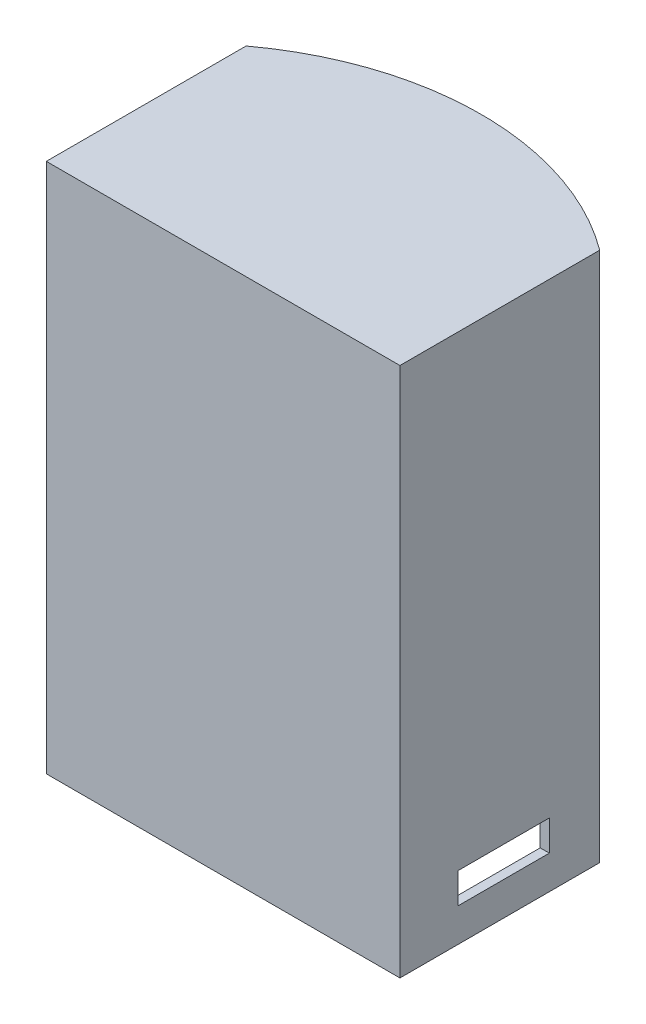
SolidWorks part; units mm, degrees
ref_plane "Front Plane" through (0, 0, 0) normal (0, 0, 1) x (1, 0, 0)
ref_plane "Top Plane" through (0, 0, 0) normal (0, 1, 0) x (1, 0, 0)
ref_plane "Right Plane" through (0, 0, 0) normal (1, 0, 0) x (0, 0, -1)
sketch "Sketch1" plane through (0, 0, 0) normal (0, 1, 0) x (1, 0, 0)
  line L0 (-29, -15) -> (-29, 15.7626)
  line L1 (-27.5, -15) -> (-16, -15)
  line L2 (-27.5, -15) -> (-27.5, 15)
  line L3 (29, -15) -> (29, 15.7626)
  line L4 (27.5, -15) -> (27.5, 15)
  line L5 (-27.5, -15) -> (27.5, 15) construction
  line L6 (-27.5, 15) -> (27.5, -15) construction
  line L8 (16, -15) -> (27.5, -15)
  line L9 (-27.5, -17) -> (-16, -17)
  line L10 (-16, -15) -> (-16, -17)
  line L12 (27.5, -17) -> (29, -17)
  line L13 (27.5, -17) -> (16, -17)
  line L14 (16, -15) -> (16, -17)
  line L15 (-29, -15) -> (-29, -17)
  line L16 (-29, -17) -> (-27.5, -17)
  line L17 (29, -17) -> (29, -15)
  arc A0 (-27.5, 15) -> (27.5, 15) centre (0, -23.3475) cw
  arc A1 (-29, 15.7626) -> (29, 15.7626) centre (0, -23.3475) cw
  point P0 (0, 0)
  dimension "D1" = 55
  dimension "D2" = 30
  dimension "D3" = 2
  dimension "D4" = 2
  dimension "D5" = 32
  dimension "D6" = 1.5
extrude "Boss-Extrude1" add sketch "Sketch1" along normal blind 85
sketch "Sketch3" plane through (0, 85, 0) normal (0, 1, 0) x (1, 0, 0)
  line L0 (-16, -17) -> (16, -17)
  line L10 (27.5, 15) -> (27.5, -15)
  line L11 (27.5, -15) -> (16, -15)
  line L12 (16, -15) -> (16, -17)
  line L13 (16, -17) -> (29, -17)
  line L14 (29, -17) -> (29, 15.7626)
  line L15 (-29, 15.7626) -> (-29, -17)
  line L16 (-29, -17) -> (-16, -17)
  line L17 (-16, -17) -> (-16, -15)
  line L18 (-16, -15) -> (-27.5, -15)
  line L19 (-27.5, -15) -> (-27.5, 15)
  line L23 (16, -17) -> (29, -17)
  line L24 (29, -17) -> (29, 15.7626)
  line L25 (-29, 15.7626) -> (-29, -17)
  line L26 (-29, -17) -> (-16, -17)
  arc A2 (27.5, 15) -> (-27.5, 15) centre (0, -23.3475) ccw
  arc A3 (29, 15.7626) -> (-29, 15.7626) centre (0, -23.3475) ccw
  arc A5 (29, 15.7626) -> (-29, 15.7626) centre (0, -23.3475) ccw
  dimension "D1" = 0
extrude "Boss-Extrude3" add sketch "Sketch3" along normal blind 2
sketch "Sketch4" plane through (0, 0, 17) normal (0, 0, 1) x (1, 0, 0)
  line L1 (-29, 87) -> (-21, 87)
  line L2 (-29, 87) -> (-29, 79)
  line L3 (-29, 79) -> (-21, 79)
  line L4 (-21, 87) -> (-21, 79)
  line L5 (29, 87) -> (21, 87)
  line L6 (29, 87) -> (29, 79)
  line L7 (29, 79) -> (21, 79)
  line L8 (21, 87) -> (21, 79)
  dimension "D1" = 8
  dimension "D2" = 8
  dimension "D3" = 8
  dimension "D4" = 8
sketch "Sketch5" plane through (0, 0, 17) normal (0, 0, 1) x (1, 0, 0)
  line L1 (-29, 0) -> (-21, 0)
  line L2 (-29, 0) -> (-29, 8)
  line L3 (-29, 8) -> (-21, 8)
  line L4 (-21, 0) -> (-21, 8)
  line L5 (29, 0) -> (21, 0)
  line L6 (29, 0) -> (29, 8)
  line L7 (29, 8) -> (21, 8)
  line L8 (21, 0) -> (21, 8)
  dimension "D1" = 8
  dimension "D2" = 8
  dimension "D3" = 8
  dimension "D4" = 8
sketch "Sketch9" plane through (0, 0, 15) normal (0, 0, -1) x (-1, 0, 0)
  line L0 (-27.5, 85) -> (-27.5, 0) construction
  line L1 (-27.5, 14) -> (-16, 14)
  line L2 (-27.5, 14) -> (-27.5, 16)
  line L3 (-27.5, 16) -> (-16, 16)
  line L4 (-16, 14) -> (-16, 16)
  line L5 (-16, 85) -> (-16, 0) construction
  line L6 (-27.5, 0) -> (-16, 0) construction
  line L7 (27.5, 85) -> (27.5, 0) construction
  line L8 (27.5, 14) -> (16, 14)
  line L9 (27.5, 14) -> (27.5, 16)
  line L10 (27.5, 16) -> (16, 16)
  line L11 (16, 14) -> (16, 16)
  line L12 (16, 85) -> (16, 0) construction
  dimension "D1" = 2
  dimension "D2" = 14
extrude "Boss-Extrude8" add sketch "Sketch9" along normal blind 3
chamfer "Chamfer1" distance 3 angle 45 2 edges at (-21.75, 14, 15) (21.75, 14, 15)
sketch "Sketch10" plane through (0, 0, 17) normal (0, 0, 1) x (1, 0, 0)
  line L1 (-16, 85) -> (16, 85)
  line L2 (-16, 85) -> (-16, 0)
  line L3 (-16, 0) -> (16, 0)
  line L4 (16, 85) -> (16, 0)
extrude "Boss-Extrude9" add sketch "Sketch10" against normal blind 2
sketch "Sketch11" plane through (29, 0, 0) normal (1, 0, 0) x (0, 0, -1)
  line L0 (0, 31.9) -> (0, -31.9) construction
  line L1 (-7.5, 10.4855) -> (7.5, 10.4855)
  line L2 (-7.5, 10.4855) -> (-7.5, 5.4855)
  line L3 (-7.5, 5.4855) -> (7.5, 5.4855)
  line L4 (7.5, 10.4855) -> (7.5, 5.4855)
  line L5 (-7.5, 10.4855) -> (7.5, 5.4855) construction
  line L6 (-7.5, 5.4855) -> (7.5, 10.4855) construction
  point P0 (0, 7.9855)
  dimension "D1" = 5
  dimension "D2" = 15
  dimension "D3" = 0
extrude "Cut-Extrude1" cut sketch "Sketch11" against normal through all
